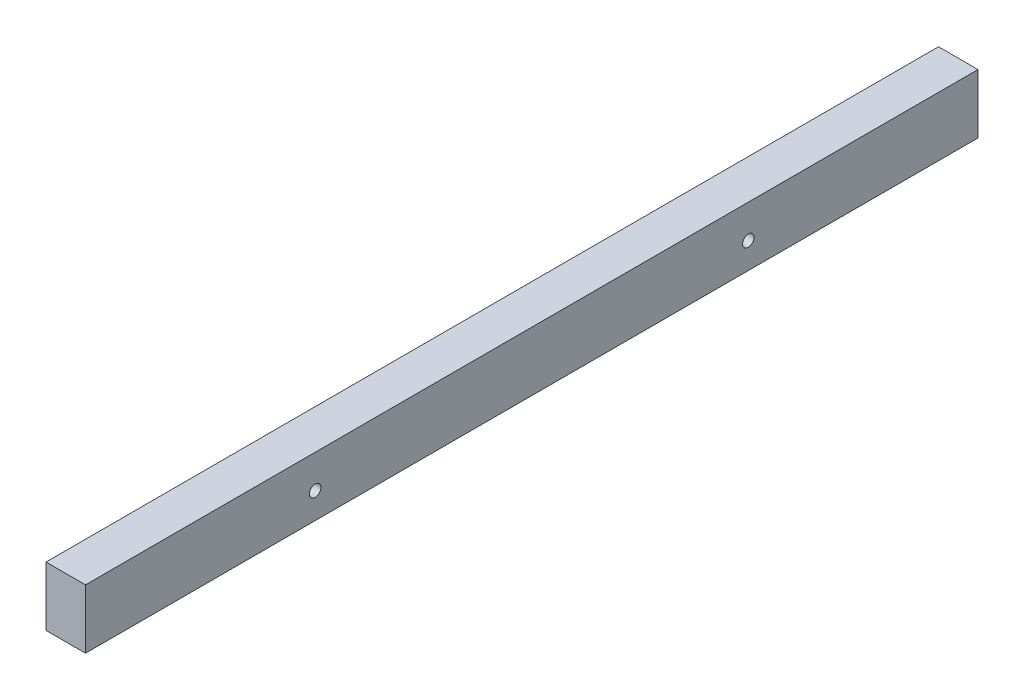
SolidWorks part; units mm, degrees
material "AISI 1020"
ref_plane "Front" through (0, 0, 0) normal (0, 0, 1) x (1, 0, 0)
ref_plane "Top" through (0, 0, 0) normal (0, 1, 0) x (1, 0, 0)
ref_plane "Right" through (0, 0, 0) normal (1, 0, 0) x (0, 0, -1)
ref_axis "side-side" through (80.9, 0, 0) along (-1, 0, 0)
ref_axis "up-down" through (0, 50, 0) along (0, -1, 0)
ref_axis "front-back" through (0, 0, -80.9) along (0, 0, 1)
sketch "Sketch1" plane through (0, 0, 0) normal (0, 0, 1) x (1, 0, 0)
  line L1 (0, 0) -> (12.7, 0)
  line L2 (0, 0) -> (0, 19.05)
  line L3 (0, 19.05) -> (12.7, 19.05)
  line L4 (12.7, 0) -> (12.7, 19.05)
  dimension "D1" = 12.7
  dimension "D2" = 19.05
extrude "Boss-Extrude1" add sketch "Sketch1" along normal blind 287.02
sketch "Sketch2" plane through (12.7, 0, 0) normal (1, 0, 0) x (0, 0, -1)
  circle A0 centre (-73.8531, 8.3431) radius 1.85 construction
  circle A1 centre (-73.8531, 8.3431) radius 1.85
  circle A2 centre (-213.1669, 8.3431) radius 1.85 construction
  circle A3 centre (-213.1669, 8.3431) radius 1.85
extrude "Cut-Extrude1" cut sketch "Sketch2" against normal through all
